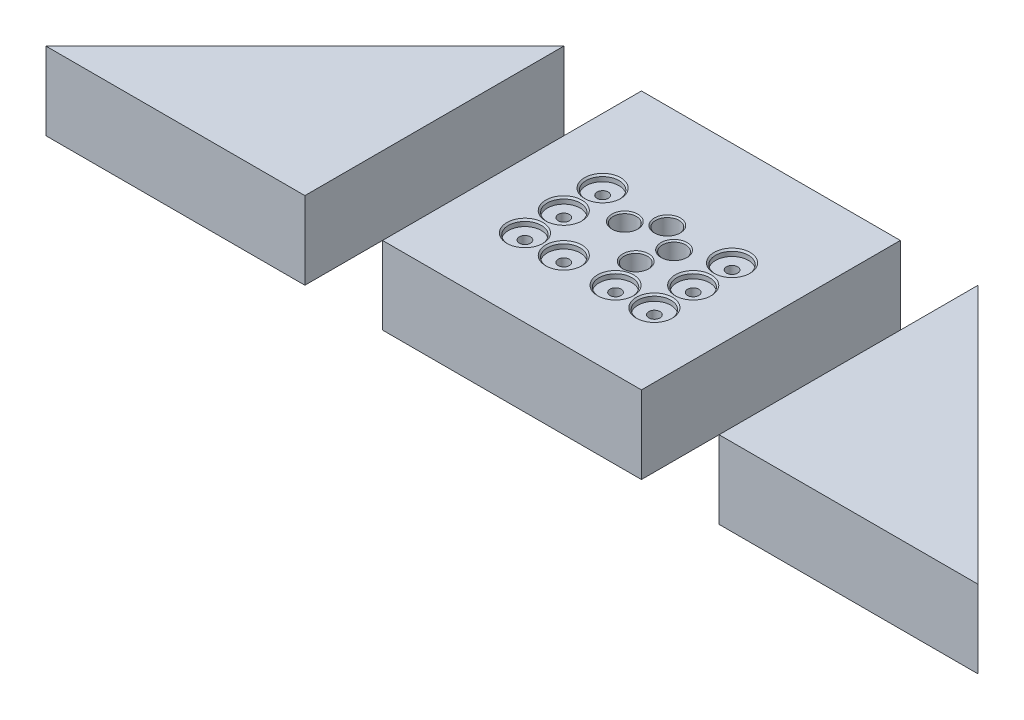
SolidWorks part; units mm, degrees
ref_plane "前视基准面" through (0, 0, 0) normal (0, 0, 1) x (1, 0, 0)
ref_plane "上视基准面" through (0, 0, 0) normal (0, 1, 0) x (1, 0, 0)
ref_plane "右视基准面" through (0, 0, 0) normal (1, 0, 0) x (0, 0, -1)
other "Configuration Table"
sketch "草图2" plane through (0, 0, 0) normal (0, 1, 0) x (1, 0, 0)
  line L0 (80, 50) -> (80, -50)
  line L1 (-50, -50) -> (50, -50)
  line L2 (-50, -50) -> (-50, 50)
  line L3 (-50, 50) -> (50, 50)
  line L4 (50, -50) -> (50, 50)
  line L5 (0, 50) -> (0, -50) construction
  line L6 (-50, 0) -> (50, 0) construction
  line L7 (80, -50) -> (180, -50)
  line L8 (180, -50) -> (80, 50)
  point P0 (0, 0)
  point P6 (109.9515, -50)
  dimension "D1" = 100
  dimension "D2" = 100
  dimension "D3" = 30
extrude "凸台-拉伸1" add sketch "草图2" along normal blind 30
hole_wizard "#6 六角头机械螺钉的柱形沉头孔1" positions "3D草图1" profile "草图3" counterbore size "#6" standard "ANSI Inch" end condition through all
sketch3d "3D草图1"
  line L0 (50, 30, -50) -> (-50, 30, -50) construction
  line L1 (-50, 30, -50) -> (-50, 30, 50) construction
  point P3 (-25, 30, -10)
  dimension "D1" = 40
  dimension "D2" = 25
sketch "草图3" plane through (-25, 30, -10) normal (1, 0, 0) x (0, 0, 1)
  line L0 (0, 0) -> (0, 30)
  line L1 (0, 30) -> (2.1526, 30)
  line L3 (2.1526, 30) -> (2.1526, 2.3622)
  line L4 (6.35, 2.3622) -> (2.1526, 2.3622)
  line L5 (6.35, 2.3622) -> (6.35, 0.635)
  line L6 (6.35, 0.635) -> (6.985, 0)
  line L7 (6.985, 0) -> (0, 0)
  line L8 (-6.35, 0.635) -> (-6.985, 0) construction
  line L11 (0, -6.35) -> (0, 107.95) construction
  dimension "通孔孔直径" = 4.3053
  dimension "通孔孔深度" = 30
  dimension "柱形沉头孔直径" = 12.7
  dimension "柱形沉头孔深度" = 2.3622
  dimension "近端锥形沉头孔直径" = 13.97
  dimension "近端锥形沉头孔角度" = 90
hole_wizard "M10x1.0 螺纹孔1" positions "草图4" profile "草图6" tap size "M10x1.0" standard "GB" end condition through all
sketch "草图4" plane through (0, 30, 0) normal (0, 1, 0) x (1, 0, 0)
  line L1 (0, 10) -> (-25, 10)
  line L4 (0, 10) -> (0, 0)
  point P0 (0, 10)
sketch "草图6" plane through (0, 30, -10) normal (1, 0, 0) x (0, 0, 1)
  line L0 (0, 0) -> (0, 30)
  line L1 (0, 30) -> (4.5, 30)
  line L2 (4.5, 30) -> (4.5, 0.525)
  line L3 (4.5, 0.525) -> (5.025, 0)
  line L5 (5.025, 0) -> (0, 0)
  line L6 (-4.5, 0.525) -> (-5.025, 0) construction
  line L11 (0, -6.35) -> (0, 107.95) construction
  dimension "通孔螺纹孔钻头直径" = 9
  dimension "通孔螺纹孔钻头深度" = 30
  dimension "近端锥形沉头孔直径" = 10.05
  dimension "近端锥形沉头孔角度" = 90
cosmetic thread "孔螺蚊线1" parameters "D2"=10
pattern_linear "阵列(线性)2" count 2 spacing 15 along (1, 0, 0) count 3 spacing 15 along (0, 0, 1) skipping (1, 0), (1, 1) of "#6 六角头机械螺钉的柱形沉头孔1"
ref_axis "基准轴1" through (0, 0, 0) along (0, 1, 0)
pattern_circular "阵列(圆周)1" count 5 over 360 about axis through (0, 0, 0) along (0, 1, 0) skipping 2 of "M10x1.0 螺纹孔1"
mirror "镜向1" about plane through (0, 0, 0) normal (1, 0, 0) of "阵列(线性)2"
mirror "镜向2" about plane through (0, 0, 0) normal (1, 0, 0) of bodies 107
